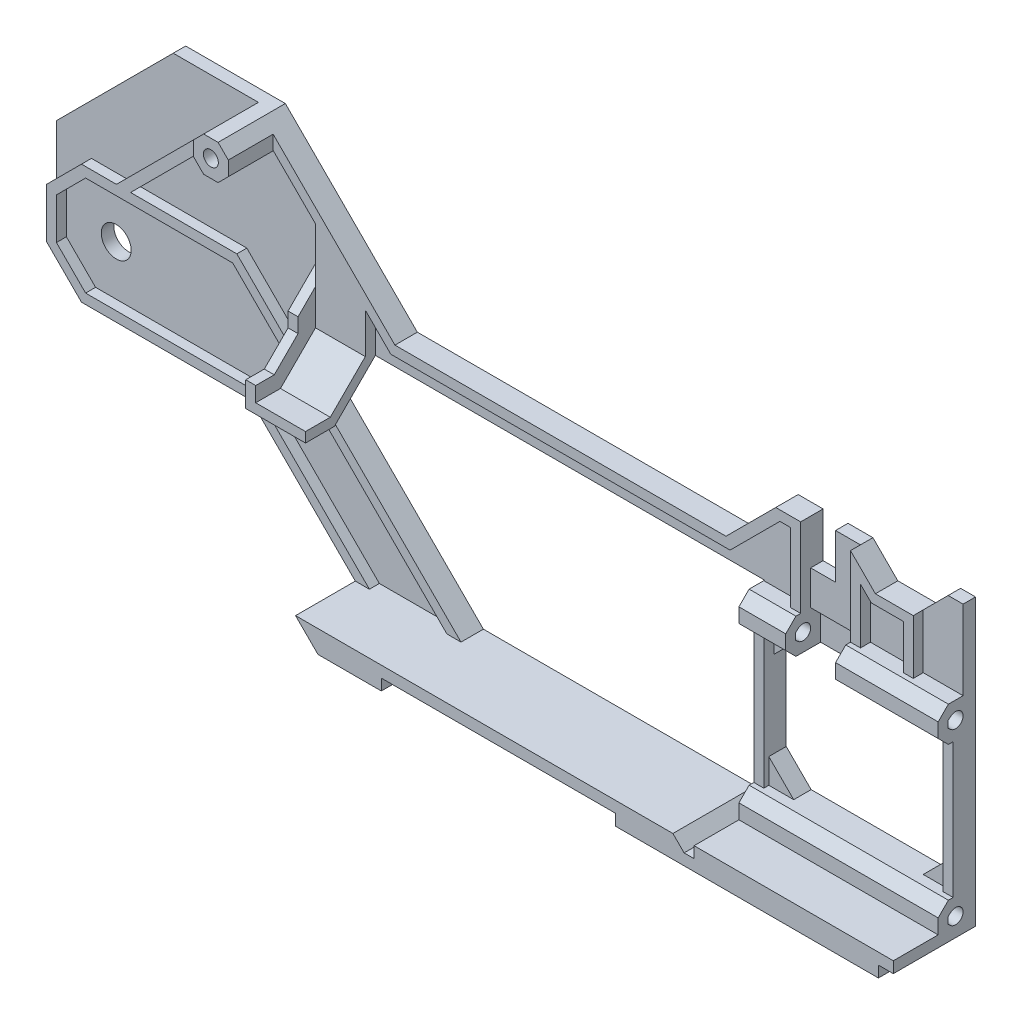
SolidWorks part; units mm, degrees
ref_plane "Front Plane" through (0, 0, 0) normal (0, 0, 1) x (1, 0, 0)
ref_plane "Top Plane" through (0, 0, 0) normal (0, 1, 0) x (1, 0, 0)
ref_plane "Right Plane" through (0, 0, 0) normal (1, 0, 0) x (0, 0, -1)
sketch "Sketch1" plane through (0, 0, 0) normal (0, 0, 1) x (1, 0, 0)
  line L0 (20, 0) -> (-100, 0) construction
  line L1 (0, 33) -> (-150, 33) construction
  line L2 (-0.6, 45) -> (-0.6, 29.0121) construction
  line L3 (20, 45) -> (20, -2.25)
  line L5 (-121, 21) -> (-95.5, -4.5)
  line L6 (-92.0503, 45) -> (20, 45)
  line L7 (17, -4.5) -> (-95.5, -4.5)
  line L9 (-78.7868, 0) -> (-24.25, 0)
  line L10 (-20, -2.25) -> (-20, 39.25)
  line L11 (-98, 39.25) -> (-20, 39.25)
  line L12 (20, 0) -> (-20, 0) construction
  line L13 (20, -4.5) -> (-100, -4.5) construction
  line L14 (-24.25, 0) -> (-22, -2.25)
  line L15 (-22, -2.25) -> (-20, -2.25)
  line L16 (20, -2.25) -> (17, -2.25)
  line L17 (17, -2.25) -> (17, -4.5)
  line L18 (-20, 0) -> (-20, -2.25) construction
  line L19 (0, 0) -> (0, 60) construction
  line L20 (-10.6, 45) -> (-10.6, 29.0121) construction
  line L21 (-5.6, 45) -> (-5.6, 33) construction
  line L22 (18, 45) -> (18, -2.25) construction
  line L23 (0, 33) -> (20, 33) construction
  line L24 (-18, 45) -> (-18, -4.5) construction
  line L25 (20, 45) -> (20, 55)
  line L27 (12, 50) -> (4.4, 50)
  line L28 (4.4, 50) -> (-0.6, 55)
  line L29 (-0.6, 55) -> (-5.6, 55)
  line L30 (-15.6, 55) -> (-25.6, 45)
  line L31 (20, 55) -> (-25.004, 55) construction
  line L32 (-10.6, 55) -> (-10.6, 46)
  line L33 (-10.6, 46) -> (-5.6, 46)
  line L34 (20, 55) -> (17, 55)
  line L35 (17, 55) -> (12, 50)
  line L36 (12, 50) -> (12, 45) construction
  line L37 (-5.6, 46) -> (-5.6, 55)
  line L38 (-10.6, 55) -> (-15.6, 55)
  line L39 (-0.6, 55) -> (-0.6, 45) construction
  line L40 (-10.6, 46) -> (-10.6, 45) construction
  line L41 (-5.6, 45) -> (-5.6, 46) construction
  line L42 (13, 32.25) -> (-13, 32.25)
  line L43 (-13, 32.25) -> (-18, 27.25)
  line L44 (-18, 27.25) -> (-18, 10)
  line L45 (-18, 10) -> (-13, 5)
  line L46 (-13, 5) -> (13, 5)
  line L47 (13, 5) -> (18, 10)
  line L48 (18, 10) -> (18, 27.25)
  line L49 (18, 27.25) -> (13, 32.25)
  line L50 (-120, 33) -> (-120, 68) construction
  line L51 (-108, 29.2132) -> (-108, 79.9918) construction
  line L52 (-116.5, 66.5503) -> (-116.5, 69.4497)
  line L53 (-116.5, 69.4497) -> (-118.5503, 71.5)
  line L54 (-118.5503, 71.5) -> (-121.4497, 71.5)
  line L55 (-121.4497, 71.5) -> (-123.5, 69.4497)
  line L56 (-123.5, 69.4497) -> (-123.5, 66.5503)
  line L57 (-123.5, 66.5503) -> (-121.4497, 64.5)
  line L58 (-121.4497, 64.5) -> (-118.5503, 64.5)
  line L59 (-118.5503, 64.5) -> (-116.5, 66.5503)
  line L60 (-145.0294, 21) -> (-121, 21)
  line L61 (-145.0294, 45) -> (-154.9706, 45)
  line L62 (-154.9706, 45) -> (-162, 37.9706)
  line L63 (-162, 37.9706) -> (-162, 28.0294)
  line L64 (-162, 28.0294) -> (-154.9706, 21)
  line L65 (-154.9706, 21) -> (-145.0294, 21)
  line L66 (-145.0294, 21) -> (-138, 28.0294)
  line L67 (-138, 28.0294) -> (-138, 37.9706)
  line L68 (-138, 37.9706) -> (-145.0294, 45)
  line L69 (-121.4497, 71.5) -> (-138.5503, 71.5)
  line L72 (-116.5, 69.4497) -> (-92.0503, 45)
  line L73 (-162, 37.9706) -> (-162, 48.0503)
  line L74 (-162, 48.0503) -> (-138.5503, 71.5)
  line L75 (-98, 33) -> (-98, 50.9497) construction
  line L76 (-78.7868, 0) -> (-108, 29.2132)
  line L77 (-98, 39.25) -> (-108, 29.2132)
  line L78 (-145.0294, 45) -> (-123.7868, 45) construction
  line L79 (-123.7868, 45) -> (-108, 29.2132) construction
  line L80 (-123.5, 69.4497) -> (-147.9497, 45) construction
  line L81 (-82.7868, 0) -> (-82.7868, -4.5) construction
  line L82 (-35.7868, 0) -> (-35.7868, -4.5) construction
  line L83 (-82.7868, -2.25) -> (-35.7868, -2.25) construction
  circle A0 centre (-150, 33) radius 3
  circle A2 centre (-120, 68) radius 1.5
  circle A3 centre (-120, 68) radius 3.5 construction
  circle A4 centre (-150, 33) radius 12 construction
  point P30 (0, 0)
  dimension "D5" = 6
  dimension "D6" = 100
  dimension "D12" = 20.6
  dimension "D14" = 10
  dimension "D15" = 5
  dimension "D16" = 2.25
  dimension "D27" = 9
  dimension "D28" = 5
  dimension "D37" = 3
  dimension "D38" = 7
  dimension "D40" = 24
  dimension "D1" = 33
  dimension "D2" = 4.5
  dimension "D3" = 150
  dimension "D4" = 12
  dimension "D7" = 45
  dimension "D8" = 40
  dimension "D9" = 3
  dimension "D10" = 15
  dimension "D11" = 5.75
  dimension "D13" = 27
  dimension "D17" = 2.25
  dimension "D18" = 2
  dimension "D19" = 135
  dimension "D20" = 2
  dimension "D21" = 2
  dimension "D22" = 10
  dimension "D23" = 5
  dimension "D24" = 45
  dimension "D25" = 3
  dimension "D26" = 45
  dimension "D29" = 135
  dimension "D30" = 0.75
  dimension "D31" = 5
  dimension "D32" = 135
  dimension "D33" = 135
  dimension "D34" = 5
  dimension "D35" = 30
  dimension "D36" = 35
  dimension "D39" = 4
  dimension "8" = 128
  dimension "D41" = 135
  dimension "D42" = 20
  dimension "D43" = 10
  dimension "D44" = 47
sketch "Sketch2" plane through (0, 0, 0) normal (1, 0, 0) x (0, 0, -1)
  line L0 (0, 0) -> (-16.5, 0) construction
  line L1 (0, 45) -> (0, -4.5) construction
  line L2 (0, 0) -> (0, 60) construction
  line L3 (0, 33) -> (-16.5, 33) construction
  line L4 (0, -4.5) -> (-16.5, -4.5) construction
  line L5 (0, 45) -> (-16.5, 45) construction
  line L6 (-16.5, -4.5) -> (-16.5, 59.6517) construction
  line L19 (-2.5, -4.5) -> (-2.5, 45) construction
  line L20 (-11.5294, 33) -> (-2.5, 42.0294) construction
  line L21 (-4, -0.4581) -> (-4, 3.4581) construction
  line L22 (-4, 3.4581) -> (-5.5, 2.1995) construction
  line L23 (-5.5, 2.1995) -> (-5.5, 0.8005) construction
  line L24 (-5.5, 0.8005) -> (-4, -0.4581) construction
  line L25 (-4, 33.6216) -> (-4, 37.5378) construction
  line L26 (-4, 37.5378) -> (-5.5, 36.2792) construction
  line L27 (-5.5, 36.2792) -> (-5.5, 34.8802) construction
  line L28 (-5.5, 34.8802) -> (-4, 33.6216) construction
  line L29 (0, -2.25) -> (-16.5, -2.25) construction
  line L30 (-2.5503, 39.0797) -> (0, 39.0797) construction
  line L31 (-0.5, 2.9497) -> (-2.5503, 5)
  line L32 (-2.5503, 5) -> (-5.4497, 5)
  line L33 (-5.4497, 5) -> (-7.5, 2.9497)
  line L34 (-7.5, 2.9497) -> (-7.5, 0.0503)
  line L35 (-7.5, 0.0503) -> (-5.4497, -2)
  line L36 (-5.4497, -2) -> (-2.5503, -2)
  line L37 (-2.5503, -2) -> (-0.5, 0.0503)
  line L38 (-0.5, 0.0503) -> (-0.5, 2.9497)
  line L39 (-0.5, 37.0294) -> (-2.5503, 39.0797)
  line L40 (-2.5503, 39.0797) -> (-5.4497, 39.0797)
  line L41 (-5.4497, 39.0797) -> (-7.5, 37.0294)
  line L42 (-7.5, 37.0294) -> (-7.5, 34.1299)
  line L43 (-7.5, 34.1299) -> (-5.4497, 32.0797)
  line L44 (-5.4497, 32.0797) -> (-2.5503, 32.0797)
  line L45 (-2.5503, 32.0797) -> (-0.5, 34.1299)
  line L46 (-0.5, 34.1299) -> (-0.5, 37.0294)
  line L47 (0, 32.0797) -> (-2.5503, 32.0797) construction
  line L48 (-2.5503, 5) -> (0, 5) construction
  line L49 (-7.5, -2.25) -> (-7.5, 0.0503) construction
  circle A0 centre (-4, 1.5) radius 1.5
  circle A1 centre (-4, 1.5) radius 3.5 construction
  circle A2 centre (-4, 35.5797) radius 1.5
  circle A3 centre (-4, 35.5797) radius 3.5 construction
  circle A4 centre (-16.5, 45) radius 12 construction
  dimension "D2" = 3
  dimension "D3" = 7
  dimension "D5" = 24
  dimension "D1" = 16.5
  dimension "D4" = 2.5
  dimension "D6" = 45
  dimension "D7" = 50
  dimension "D8" = 50
  dimension "D9" = 2.25
sketch "Sketch4" plane through (0, 0, 0) normal (0, 0, 1) x (1, 0, 0)
  line L0 (-92.0503, 45) -> (20, 45) construction
  line L1 (-98, 39.25) -> (-108, 29.2132) construction
  line L2 (-121, 21) -> (-95.5, -4.5) construction
  line L3 (17, -4.5) -> (-95.5, -4.5) construction
  line L4 (-82.7868, 0) -> (-82.7868, -4.5) construction
  line L5 (-98, 39.25) -> (-20, 39.25) construction
  line L6 (-20, -2.25) -> (-20, 39.25) construction
  line L7 (-22, -2.25) -> (-20, -2.25) construction
  line L8 (-24.25, 0) -> (-22, -2.25) construction
  line L9 (-78.7868, 0) -> (-24.25, 0) construction
  line L10 (17, -2.25) -> (17, -4.5) construction
  line L11 (20, -2.25) -> (17, -2.25) construction
  line L12 (20, 45) -> (20, -2.25) construction
  line L13 (-92.0503, 45) -> (-25.6, 45)
  line L14 (-145.0294, 21) -> (-121, 21) construction
  line L15 (-121, 21) -> (-95.5, -4.5)
  line L16 (17, -4.5) -> (-35.7868, -4.5)
  line L17 (-78.7868, 0) -> (-108, 29.2132) construction
  line L18 (-98, 39.25) -> (-20, 39.25)
  line L19 (-20, -2.25) -> (-20, 39.25)
  line L20 (-22, -2.25) -> (-20, -2.25)
  line L21 (-24.25, 0) -> (-22, -2.25)
  line L22 (-78.7868, 0) -> (-24.25, 0)
  line L23 (17, -2.25) -> (17, -4.5)
  line L24 (20, -2.25) -> (17, -2.25)
  line L25 (20, 45) -> (20, -2.25)
  line L26 (-116.5, 69.4497) -> (-92.0503, 45) construction
  line L27 (-0.6, 55) -> (-5.6, 55) construction
  line L28 (4.4, 50) -> (-0.6, 55) construction
  line L29 (12, 50) -> (4.4, 50) construction
  line L30 (-98, 39.25) -> (-108, 29.2132)
  line L31 (20, 45) -> (20, 55) construction
  line L32 (-15.6, 55) -> (-25.6, 45) construction
  line L33 (-0.6, 55) -> (-5.6, 55)
  line L34 (4.4, 50) -> (-0.6, 55)
  line L35 (12, 50) -> (4.4, 50)
  line L36 (-10.6, 55) -> (-15.6, 55) construction
  line L37 (20, 45) -> (20, 55)
  line L38 (-10.6, 55) -> (-10.6, 46) construction
  line L39 (-10.6, 46) -> (-5.6, 46) construction
  line L40 (-5.6, 46) -> (-5.6, 55) construction
  line L41 (17, 55) -> (12, 50) construction
  line L42 (20, 55) -> (17, 55) construction
  line L43 (-15.6, 55) -> (-25.6, 45)
  line L44 (-10.6, 55) -> (-15.6, 55)
  line L45 (-10.6, 55) -> (-10.6, 46)
  line L46 (-10.6, 46) -> (-5.6, 46)
  line L47 (-5.6, 46) -> (-5.6, 55)
  line L48 (17, 55) -> (12, 50)
  line L49 (20, 55) -> (17, 55)
  line L50 (13, 32.25) -> (-13, 32.25) construction
  line L51 (-13, 32.25) -> (-18, 27.25) construction
  line L52 (-18, 27.25) -> (-18, 10) construction
  line L53 (-18, 10) -> (-13, 5) construction
  line L54 (-13, 5) -> (13, 5) construction
  line L55 (13, 5) -> (18, 10) construction
  line L56 (18, 10) -> (18, 27.25) construction
  line L57 (18, 27.25) -> (13, 32.25) construction
  line L58 (13, 32.25) -> (-13, 32.25)
  line L59 (-13, 32.25) -> (-18, 27.25)
  line L60 (-18, 27.25) -> (-18, 10)
  line L61 (-18, 10) -> (-13, 5)
  line L62 (-13, 5) -> (13, 5)
  line L63 (13, 5) -> (18, 10)
  line L64 (18, 10) -> (18, 27.25)
  line L65 (18, 27.25) -> (13, 32.25)
  line L66 (-118.5503, 71.5) -> (-121.4497, 71.5) construction
  line L67 (-121.4497, 71.5) -> (-138.5503, 71.5) construction
  line L68 (-78.7868, 0) -> (-108, 29.2132)
  line L69 (-82.7868, -2.25) -> (-35.7868, -2.25) construction
  line L70 (-162, 37.9706) -> (-162, 28.0294) construction
  line L71 (-162, 28.0294) -> (-154.9706, 21) construction
  line L72 (-154.9706, 21) -> (-145.0294, 21) construction
  line L73 (-116.5, 69.4497) -> (-92.0503, 45)
  line L74 (-116.5, 69.4497) -> (-118.5503, 71.5) construction
  line L75 (-118.5503, 71.5) -> (-121.4497, 71.5)
  line L76 (-121.4497, 71.5) -> (-138.5503, 71.5)
  line L77 (-162, 48.0503) -> (-138.5503, 71.5) construction
  line L78 (-162, 37.9706) -> (-162, 48.0503) construction
  line L79 (-162, 37.9706) -> (-162, 28.0294)
  line L80 (-162, 28.0294) -> (-154.9706, 21)
  line L81 (-154.9706, 21) -> (-145.0294, 21)
  line L82 (-145.0294, 21) -> (-121, 21)
  line L83 (-116.5, 69.4497) -> (-118.5503, 71.5)
  line L84 (-162, 48.0503) -> (-138.5503, 71.5)
  line L85 (-162, 37.9706) -> (-162, 48.0503)
  line L86 (-35.7868, 0) -> (-35.7868, -4.5) construction
  line L87 (-82.7868, -2.25) -> (-82.7868, -4.5)
  line L88 (-82.7868, -2.25) -> (-35.7868, -2.25)
  line L89 (-35.7868, -2.25) -> (-35.7868, -4.5)
  line L90 (-82.7868, -4.5) -> (-95.5, -4.5)
  circle A1 centre (-150, 33) radius 3 construction
  circle A3 centre (-150, 33) radius 3
extrude "Boss-Extrude1" add sketch "Sketch4" along normal up to vertex (2.5 mm away) up to point (0, 45, 2.5)
sketch "Sketch5" plane through (0, 0, 2.5) normal (0, 0, 1) x (1, 0, 0)
  line L0 (20, 45) -> (20, -2.25) construction
  line L1 (20, -2.25) -> (17, -2.25) construction
  line L2 (17, -2.25) -> (17, -4.5) construction
  line L3 (17, -4.5) -> (-95.5, -4.5) construction
  line L4 (-121, 21) -> (-95.5, -4.5) construction
  line L5 (20, 0) -> (-100, 0) construction
  line L6 (-24.25, 0) -> (-22, -2.25) construction
  line L7 (-22, -2.25) -> (-20, -2.25) construction
  line L8 (-20, -2.25) -> (-20, 39.25) construction
  line L9 (20, 0) -> (20, -2.25)
  line L10 (20, -2.25) -> (17, -2.25)
  line L11 (17, -2.25) -> (17, -4.5)
  line L12 (17, -4.5) -> (-35.7868, -4.5)
  line L13 (-100, 0) -> (-95.5, -4.5)
  line L14 (20, 0) -> (-20, 0)
  line L15 (-24.25, 0) -> (-22, -2.25)
  line L16 (-22, -2.25) -> (-20, -2.25)
  line L17 (-20, -2.25) -> (-20, 0)
  line L18 (-24.25, 0) -> (-100, 0)
  line L19 (-82.7868, 0) -> (-82.7868, -4.5) construction
  line L20 (-82.7868, -2.25) -> (-35.7868, -2.25) construction
  line L21 (-35.7868, 0) -> (-35.7868, -4.5) construction
  line L22 (-82.7868, -2.25) -> (-82.7868, -4.5)
  line L23 (-82.7868, -2.25) -> (-35.7868, -2.25)
  line L24 (-35.7868, -2.25) -> (-35.7868, -4.5)
  line L25 (-82.7868, -4.5) -> (-95.5, -4.5)
extrude "Boss-Extrude2" add sketch "Sketch5" along normal up to vertex (14 mm away) up to point (0, -4.5, 16.5)
sketch "Sketch6" plane through (0, 0, 0) normal (1, 0, 0) x (0, 0, -1)
  line L12 (-4, 37.5378) -> (-5.5, 36.2792) construction
  line L13 (-5.5, 36.2792) -> (-5.5, 34.8802) construction
  line L14 (-5.5, 34.8802) -> (-4, 33.6216) construction
  line L15 (-4, 3.4581) -> (-5.5, 2.1995) construction
  line L16 (-5.5, 2.1995) -> (-5.5, 0.8005) construction
  line L17 (-5.5, 0.8005) -> (-4, -0.4581) construction
  line L18 (-7.5, 34.1299) -> (-5.4497, 32.0797) construction
  line L19 (-7.5, 37.0294) -> (-7.5, 34.1299) construction
  line L20 (-5.4497, 39.0797) -> (-7.5, 37.0294) construction
  line L21 (-5.4497, 32.0797) -> (-2.5503, 32.0797) construction
  line L25 (-2.5503, 39.0797) -> (-5.4497, 39.0797) construction
  line L29 (-7.5, 2.9497) -> (-7.5, 0.0503) construction
  line L30 (-4.9642, 36.7288) -> (-5.5, 36.2792)
  line L31 (-5.5, 36.2792) -> (-5.5, 34.8802)
  line L32 (-5.5, 34.8802) -> (-4.9642, 34.4306)
  line L33 (-4.9642, 2.6491) -> (-5.5, 2.1995)
  line L34 (-5.5, 2.1995) -> (-5.5, 0.8005)
  line L35 (-5.5, 0.8005) -> (-4.9642, 0.3509)
  line L36 (-5.4497, 5) -> (-7.5, 2.9497) construction
  line L37 (-2.5503, 5) -> (-5.4497, 5) construction
  line L40 (-7.5, 34.1299) -> (-5.4497, 32.0797)
  line L41 (-7.5, 37.0294) -> (-7.5, 34.1299)
  line L42 (-5.4497, 39.0797) -> (-7.5, 37.0294)
  line L43 (-5.4497, 32.0797) -> (-2.5503, 32.0797)
  line L44 (0, 5) -> (0, -2.25)
  line L47 (-2.5503, 39.0797) -> (-5.4497, 39.0797)
  line L48 (-2.5503, 39.0797) -> (0, 39.0797) construction
  line L49 (0, 32.0797) -> (-2.5503, 32.0797) construction
  line L50 (-2.5503, 39.0797) -> (0, 39.0797)
  line L51 (-7.5, 2.9497) -> (-7.5, 0.0503)
  line L52 (-5.4497, 5) -> (-7.5, 2.9497)
  line L53 (-2.5503, 5) -> (-5.4497, 5)
  line L54 (0, 32.0797) -> (-2.5503, 32.0797)
  line L56 (-2.5503, 5) -> (0, 5) construction
  line L57 (-7.5, -2.25) -> (-7.5, 0.0503) construction
  line L58 (0, 45) -> (0, -4.5) construction
  line L59 (0, -2.25) -> (-16.5, -2.25) construction
  line L60 (-2.5503, 5) -> (0, 5)
  line L61 (-7.5, -2.25) -> (-7.5, 0.0503)
  line L62 (0, 39.0797) -> (0, 32.0797)
  line L63 (0, -2.25) -> (-7.5, -2.25)
  circle A0 centre (-4, 35.5797) radius 1.5 construction
  circle A1 centre (-4, 1.5) radius 1.5 construction
  arc A2 (-4.9642, 34.4306) -> (-4.9642, 36.7288) centre (-4, 35.5797) ccw
  arc A3 (-4.9642, 0.3509) -> (-4.9642, 2.6491) centre (-4, 1.5) ccw
extrude "Boss-Extrude3" add sketch "Sketch6" along normal mid plane 40
sketch "Sketch8" plane through (0, 0, 7.5) normal (0, 0, 1) x (1, 0, 0)
  line L0 (-20, 39.0797) -> (20, 39.0797) construction
  line L1 (20, 32.0797) -> (13.1703, 32.0797) construction
  line L2 (-10.6, 39.0797) -> (-0.6, 39.0797)
  line L3 (-0.6, 32.0797) -> (-10.6, 32.0797)
  line L4 (20, 45) -> (20, -2.25) construction
  line L5 (20, 45) -> (20, -2.25) construction
  line L6 (-10.6, 45) -> (-10.6, 29.0121) construction
  line L7 (-0.6, 45) -> (-0.6, 29.0121) construction
  line L8 (-10.6, 39.0797) -> (-10.6, 32.0797)
  line L9 (-0.6, 39.0797) -> (-0.6, 32.0797)
extrude "Cut-Extrude2" cut sketch "Sketch8" against normal up to vertex (7 mm away) up to point (0, 34.1299, 0.5)
ref_plane "Plane1" through (-108, 0, 0) normal (1, 0, 0) x (0, 0, -1)
sketch "Sketch9" plane through (0, 0, 2.5) normal (0, 0, 1) x (1, 0, 0)
  line L0 (-20, -2.25) -> (-20, 39.25) construction
  line L2 (-10.6, 32.0797) -> (-20, 32.0797) construction
  line L3 (-20, 5) -> (-13, 5) construction
  line L4 (18, 45) -> (18, -2.25) construction
  line L5 (20, 45) -> (20, -2.25) construction
  line L6 (13, 5) -> (20, 5) construction
  line L7 (20, 32.0797) -> (13.1703, 32.0797) construction
  line L8 (-20, 5) -> (-20, 32.0797)
  line L9 (-18, 45) -> (-18, -4.5) construction
  line L10 (-18, 32.0797) -> (-20, 32.0797)
  line L11 (-20, 5) -> (-18, 5)
  line L12 (18, 32.0797) -> (18, 5)
  line L13 (20, 32.0797) -> (20, 5)
  line L14 (18, 5) -> (20, 5)
  line L15 (20, 32.0797) -> (18, 32.0797)
  line L16 (-18, 32.0797) -> (-18, 5)
  line L17 (12, 50) -> (12, 45) construction
  line L18 (12, 50) -> (4.4, 50) construction
  line L19 (4.4, 50) -> (-0.6, 55) construction
  line L20 (-0.6, 55) -> (-0.6, 45) construction
  line L21 (-0.6, 45) -> (-0.6, 29.0121) construction
  line L22 (-10.6, 45) -> (-10.6, 29.0121) construction
  line L23 (-10.6, 46) -> (-10.6, 45) construction
  line L24 (-10.6, 55) -> (-10.6, 46) construction
  line L25 (-10.6, 55) -> (-15.6, 55) construction
  line L26 (-15.6, 55) -> (-25.6, 45) construction
  line L27 (-92.0503, 45) -> (20, 45) construction
  line L28 (12, 50) -> (12, 45)
  line L29 (12, 50) -> (4.4, 50)
  line L30 (4.4, 50) -> (-0.6, 55)
  line L31 (-0.6, 55) -> (-0.6, 45)
  line L32 (-0.6, 45) -> (-0.6, 39.0797)
  line L33 (-10.6, 45) -> (-10.6, 39.0797)
  line L34 (-10.6, 46) -> (-10.6, 45)
  line L35 (-10.6, 55) -> (-10.6, 46)
  line L36 (-10.6, 55) -> (-15.6, 55)
  line L37 (-15.6, 55) -> (-25.6, 45)
  line L38 (-22.7716, 45) -> (-24.7716, 43)
  line L39 (-12.6, 53) -> (-12.6, 39.0797)
  line L40 (-98, 33) -> (-98, 50.9497) construction
  line L41 (-12.6, 53) -> (-14.7716, 53)
  line L42 (-14.7716, 53) -> (-22.7716, 45)
  line L44 (-14.7716, 53) -> (-24.1858, 43.5858) construction
  line L45 (1.4, 45) -> (1.4, 39.0797)
  line L46 (-20, 39.0797) -> (-10.6, 39.0797) construction
  line L47 (-12.6, 39.0797) -> (-10.6, 39.0797)
  line L48 (-0.6, 39.0797) -> (20, 39.0797) construction
  line L49 (-108, 29.2132) -> (-108, 79.9918) construction
  line L50 (-123.7868, 45) -> (-108, 29.2132) construction
  line L51 (-0.6, 39.0797) -> (1.4, 39.0797)
  line L52 (12, 45) -> (12, 39.0797)
  line L53 (10, 45) -> (10, 39.0797)
  line L54 (10, 48) -> (10, 45)
  line L55 (10, 48) -> (3.5716, 48)
  line L56 (3.5716, 48) -> (1.4, 50.1716)
  line L57 (1.4, 50.1716) -> (1.4, 45)
  line L58 (-145.0294, 45) -> (-123.7868, 45) construction
  line L59 (10, 39.0797) -> (12, 39.0797)
  line L60 (-0.6, 45) -> (-0.6, 29.0121) construction
  line L61 (1.4, 45) -> (1.4, 29.0121) construction
  line L62 (-12.6, 46) -> (-12.6, 45) construction
  line L63 (-12.6, 53) -> (-12.6, 46) construction
  line L64 (-145.0294, 45) -> (-154.9706, 45) construction
  line L65 (-154.9706, 45) -> (-162, 37.9706) construction
  line L66 (-162, 37.9706) -> (-162, 28.0294) construction
  line L67 (-162, 28.0294) -> (-154.9706, 21) construction
  line L68 (-154.9706, 21) -> (-145.0294, 21) construction
  line L69 (-145.0294, 21) -> (-121, 21) construction
  line L70 (-121, 21) -> (-95.5, -4.5) construction
  line L71 (-78.7868, 0) -> (-108, 29.2132) construction
  line L72 (-92.0503, 45) -> (-25.6, 45)
  line L73 (-116.5, 69.4497) -> (-92.0503, 45) construction
  line L74 (-98, 39.25) -> (-98, 48.1213)
  line L75 (-116.5, 69.4497) -> (-92.0503, 45)
  line L76 (-108, 32.0468) -> (-108, 58.1213)
  line L77 (-123.7868, 45) -> (-109.4142, 30.6274)
  line L78 (-145.0294, 45) -> (-123.7868, 45)
  line L79 (-145.0294, 45) -> (-145.1213, 45)
  line L80 (-154.9706, 45) -> (-162, 37.9706)
  line L81 (-162, 37.9706) -> (-162, 28.0294)
  line L82 (-162, 28.0294) -> (-154.9706, 21)
  line L83 (-154.9706, 21) -> (-145.0294, 21)
  line L84 (-145.0294, 21) -> (-121, 21)
  line L85 (-121, 21) -> (-100, 0)
  line L86 (-78.7868, 0) -> (-108, 29.2132)
  line L87 (-124.6152, 43) -> (-109.4142, 27.799)
  line L88 (-145.0294, 43) -> (-124.6152, 43)
  line L89 (-145.0294, 43) -> (-154.1421, 43)
  line L90 (-154.1421, 43) -> (-160, 37.1421)
  line L91 (-160, 37.1421) -> (-160, 28.8579)
  line L92 (-160, 28.8579) -> (-154.1421, 23)
  line L93 (-154.1421, 23) -> (-145.0294, 23)
  line L94 (-145.0294, 23) -> (-120.1716, 23)
  line L95 (-120.1716, 23) -> (-97.1716, 0)
  line L96 (-81.6152, 0) -> (-109.4142, 27.799)
  line L97 (-109.4142, 30.6274) -> (-108, 32.0468)
  line L98 (-116.5, 66.6213) -> (-108, 58.1213)
  line L99 (-92.8787, 43) -> (-24.7716, 43)
  line L101 (20, 0) -> (-100, 0) construction
  line L102 (-78.7868, 0) -> (-81.6152, 0)
  line L103 (-97.1716, 0) -> (-100, 0)
  line L104 (-80.201, -1.4142) -> (-109.4142, 27.799) construction
  line L105 (-98, 48.1213) -> (-92.8787, 43)
  line L106 (-120.1716, 23) -> (-94.0858, -3.0858) construction
  line L107 (-121, 21) -> (-95.5, -4.5) construction
  line L109 (-123.7868, 45) -> (-108, 29.2132) construction
  line L110 (-116.5, 66.5503) -> (-116.5, 69.4497) construction
  line L111 (-117.9142, 68.0355) -> (-92.8787, 43) construction
  line L113 (-116.5, 66.6213) -> (-116.5, 69.4497)
  line L114 (-116.5, 69.4497) -> (-92.0503, 45) construction
  line L116 (-123.5, 69.4497) -> (-147.9497, 45) construction
  line L118 (-92.0503, 45) -> (20, 45) construction
  line L120 (-92.8787, 43) -> (20, 43) construction
  line L121 (-123.5, 69.4497) -> (-123.5, 66.5503) construction
  line L122 (-123.5, 69.4497) -> (-147.9497, 45)
  line L123 (-123.5, 69.4497) -> (-123.5, 66.6213)
  line L124 (-123.5, 66.6213) -> (-145.1213, 45)
  line L125 (-147.9497, 45) -> (-154.9706, 45)
  line L126 (-122.0858, 68.0355) -> (-146.5355, 43.5858) construction
  line L127 (-98, 39.25) -> (-108, 29.2132) construction
  line L128 (-145.0294, 45) -> (-154.9706, 45) construction
  line L129 (-98, 39.25) -> (-108, 29.2132)
  point P39 (-12.6, 45)
  point P40 (-12.6, 21.375)
  point P83 (-110, 29.2132)
  point P84 (-110, 79.9918)
  point P88 (-96, 33)
  point P89 (-96, 50.9497)
  dimension "D7" = 2
  dimension "D4" = 2
  dimension "D1" = 2
  dimension "D2" = 2
  dimension "D3" = 2
  dimension "D5" = 2
extrude "Boss-Extrude4" add sketch "Sketch9" along normal blind 2
sketch "Sketch12" plane through (-108, 0, 0) normal (1, 0, 0) x (0, 0, -1)
  line L0 (-11.5294, 33) -> (-2.5, 42.0294) construction
  line L1 (0, 33) -> (-16.5, 33) construction
  line L2 (-16.5, -4.5) -> (-16.5, 59.6517) construction
  line L3 (0, 45) -> (-16.5, 45) construction
  line L4 (-11.5294, 33) -> (-4.5, 40.0294)
  line L5 (-11.5294, 33) -> (-16.5, 33)
  line L6 (-16.5, -4.5) -> (-16.5, 59.6517) construction
  line L7 (0, 45) -> (-16.5, 45) construction
  line L8 (-10.701, 31) -> (-16.5, 31)
  line L9 (-16.5, 33) -> (-16.5, 31)
  line L11 (0, 48.0503) -> (0, 71.5) construction
  line L12 (0, 49.701) -> (-4.5, 49.701)
  line L13 (-4.5, 50) -> (-4.5, 55) construction
  line L14 (-4.5, 49.701) -> (-4.5, 40.0294)
  line L15 (-4.5, 39.0797) -> (-4.5, 50) construction
  line L16 (0, -2.25) -> (0, 55) construction
  line L17 (0, 33) -> (-16.5, 33) construction
  line L18 (0, 41.701) -> (0, 49.701)
  line L19 (-10.701, 31) -> (0, 41.701)
  line L21 (0, 31) -> (-16.5, 31) construction
  circle A0 centre (-16.5, 45) radius 12 construction
  circle A1 centre (-16.5, 45) radius 12 construction
  dimension "D3" = 8
  dimension "D2" = 2
  dimension "D1" = 2
extrude "Boss-Extrude6" add sketch "Sketch12" along normal blind 10
sketch "Sketch15" plane through (-108, 0, 0) normal (1, 0, 0) x (0, 0, -1)
  line L0 (0, 0) -> (0, 60) construction
  line L1 (0, 33) -> (-16.5, 33) construction
  line L2 (-11.5294, 33) -> (-2.5, 42.0294) construction
  line L3 (-16.5, -4.5) -> (-16.5, 59.6517) construction
  line L4 (0, 41.701) -> (0, 51.701)
  line L5 (0, 33) -> (-16.5, 33) construction
  line L6 (-11.5294, 33) -> (-2.5, 42.0294) construction
  line L7 (-16.5, 31) -> (-16.5, 36)
  line L8 (0, 51.701) -> (-8, 43.701)
  line L9 (-8, 43.701) -> (-8, 40.7721)
  line L10 (-8, 40.7721) -> (-12.7721, 36)
  line L11 (-12.7721, 36) -> (-16.5, 36)
  line L12 (-16.5, 31) -> (-10.701, 31)
  line L13 (-10.701, 31) -> (0, 41.701)
  circle A0 centre (-16.5, 45) radius 12 construction
  circle A1 centre (-16.5, 45) radius 12 construction
  dimension "D1" = 2
  dimension "D2" = 3
  dimension "D3" = 8
  dimension "D4" = 2
  dimension "D5" = 3
  dimension "D6" = 10
extrude "Boss-Extrude8" add sketch "Sketch15" against normal blind 2
sketch "Sketch10" plane through (0, 0, 2.5) normal (0, 0, 1) x (1, 0, 0)
  line L0 (-121.4497, 71.5) -> (-123.5, 69.4497) construction
  line L1 (-123.5, 69.4497) -> (-123.5, 66.5503) construction
  line L2 (-123.5, 66.5503) -> (-121.4497, 64.5) construction
  line L3 (-121.4497, 64.5) -> (-118.5503, 64.5) construction
  line L4 (-118.5503, 64.5) -> (-116.5, 66.5503) construction
  line L5 (-116.5, 66.5503) -> (-116.5, 69.4497) construction
  line L6 (-116.5, 69.4497) -> (-118.5503, 71.5) construction
  line L7 (-118.5503, 71.5) -> (-121.4497, 71.5) construction
  line L8 (-121.4497, 71.5) -> (-123.5, 69.4497)
  line L9 (-123.5, 69.4497) -> (-123.5, 66.5503)
  line L10 (-123.5, 66.5503) -> (-121.4497, 64.5)
  line L11 (-121.4497, 64.5) -> (-118.5503, 64.5)
  line L12 (-118.5503, 64.5) -> (-116.5, 66.5503)
  line L13 (-116.5, 66.5503) -> (-116.5, 69.4497)
  line L14 (-116.5, 69.4497) -> (-118.5503, 71.5)
  line L15 (-118.5503, 71.5) -> (-121.4497, 71.5)
extrude "Boss-Extrude5" add sketch "Sketch10" along normal blind 11
sketch "Sketch11" plane through (0, 0, 13.5) normal (0, 0, 1) x (1, 0, 0)
  circle A0 centre (-120, 68) radius 1.5 construction
  circle A1 centre (-120, 68) radius 1.5
extrude "Cut-Extrude3" cut sketch "Sketch11" against normal blind 7
sketch "Sketch16" plane through (0, 0, 2.5) normal (0, 0, 1) x (1, 0, 0)
  line L0 (-18, 10) -> (-13, 5) construction
  line L1 (-18, 45) -> (-18, -4.5) construction
  line L2 (-13, 5) -> (-18, 5) construction
  line L3 (13, 5) -> (18, 10) construction
  line L4 (18, 5) -> (13, 5) construction
  line L5 (18, 45) -> (18, -2.25) construction
  line L6 (-18, 10) -> (-13, 5)
  line L7 (-18, 10) -> (-18, 5)
  line L8 (-13, 5) -> (-18, 5)
  line L9 (13, 5) -> (18, 10)
  line L10 (18, 5) -> (13, 5)
  line L11 (18, 10) -> (18, 5)
extrude "Boss-Extrude9" add sketch "Sketch16" along normal blind 1
